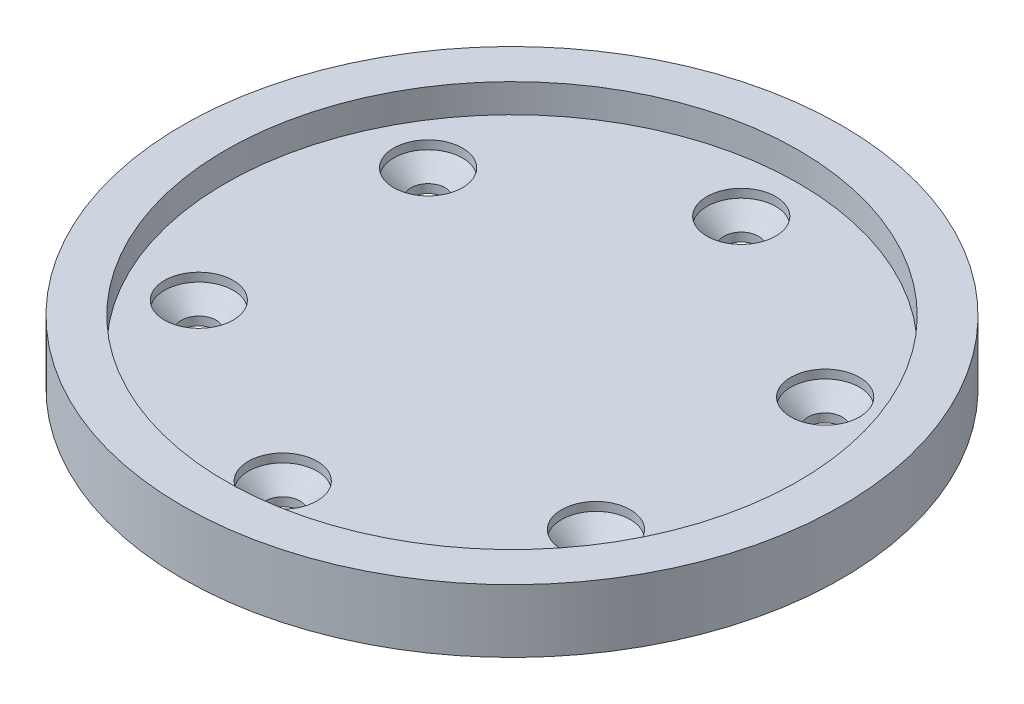
SolidWorks part; units mm, degrees
material "PBT General Purpose"
ref_plane "Front Plane" through (0, 0, 0) normal (0, 0, 1) x (1, 0, 0)
ref_plane "Top Plane" through (0, 0, 0) normal (0, 1, 0) x (1, 0, 0)
ref_plane "Right Plane" through (0, 0, 0) normal (1, 0, 0) x (0, 0, -1)
sketch "Sketch1" plane through (0, 0, 0) normal (0, 0, 1) x (1, 0, 0)
  line L0 (0, 0) -> (0, 21.4941) construction
  line L1 (50, 5.4786) -> (50, 10.4786)
  line L2 (50, 10.4786) -> (57.5, 10.4786)
  line L9 (50, 5.4786) -> (0, 5.4786)
  line L10 (0, -0.5214) -> (0, 5.4786)
  line L11 (0, -0.5214) -> (57.5, -0.5214)
  line L12 (57.5, -0.5214) -> (57.5, 10.4786)
  dimension "D1" = 0.5214
  dimension "D2" = 50
  dimension "D5" = 7.5
  dimension "D3" = 6
  dimension "D7" = 5
revolve "Revolve1" add sketch "Sketch1" angle 360 about L0
sketch "Sketch2" plane through (0, 5.4786, 0) normal (0, 1, 0) x (1, 0, 0)
  line L0 (0, 0) -> (0, 40) construction
  circle A0 centre (0, 40) radius 3
  circle A6 centre (34.641, 20) radius 3
  circle A7 centre (34.641, -20) radius 3
  circle A8 centre (0, -40) radius 3
  circle A9 centre (-34.641, -20) radius 3
  circle A10 centre (-34.641, 20) radius 3
  point P31 (0, 0)
  dimension "D1" = 6
  dimension "D2" = 40
  dimension "D3" = 6
extrude "Cut-Extrude1" cut sketch "Sketch2" against normal through all
sketch "Sketch3" plane through (0, 5.4786, 0) normal (0, 1, 0) x (1, 0, 0)
  circle A0 centre (0, 40) radius 6
  circle A1 centre (34.641, 20) radius 6
  circle A2 centre (34.641, -20) radius 6
  circle A3 centre (0, -40) radius 6
  circle A4 centre (-34.641, -20) radius 6
  circle A5 centre (-34.641, 20) radius 6
  point P3 (0, 0)
  point P18 (0, 0)
  dimension "D1" = 12
  dimension "D2" = 6
extrude "Cut-Extrude2" cut sketch "Sketch3" against normal blind 1.5
chamfer "Chamfer1" distance 3 angle 45 6 edges at (-34.641, 3.9786, -17) (-34.641, 3.9786, 23) (0, 3.9786, 43) (0, 3.9786, -37) (34.641, 3.9786, -17) (34.641, 3.9786, 23)
sketch "Avoid Area1" plane through (0, 10.4786, 0) normal (0, 1, 0) x (1, 0, 0)
  line L1 (-89.8447, 23.9111) -> (-38.4245, 23.9111)
  line L2 (-89.8447, 23.9111) -> (-89.8447, -17.7959)
  line L3 (-89.8447, -17.7959) -> (-38.4245, -17.7959)
  line L4 (-38.4245, 23.9111) -> (-38.4245, -17.7959)
  line L5 (40.0837, 23.0719) -> (89.3624, 23.0719)
  line L6 (40.0837, 23.0719) -> (40.0837, -19.2779)
  line L7 (40.0837, -19.2779) -> (89.3624, -19.2779)
  line L8 (89.3624, 23.0719) -> (89.3624, -19.2779)
sketch "Avoid Area2" plane through (0, 10.4786, 0) normal (0, 1, 0) x (1, 0, 0)
  line L5 (-29.0326, -25.7834) -> (28.925, -25.7834)
  line L6 (-29.0326, -25.7834) -> (-29.0326, -80.3919)
  line L11 (-29.0326, -80.3919) -> (28.925, -80.3919)
  line L12 (28.925, -25.7834) -> (28.925, -80.3919)
  line L13 (-25.225, 88.174) -> (28.7215, 88.174)
  line L14 (-25.225, 88.174) -> (-25.225, 29.095)
  line L15 (-25.225, 29.095) -> (28.7215, 29.095)
  line L16 (28.7215, 88.174) -> (28.7215, 29.095)
  point P0 (0, 0)
  point P6 (0, 0)
sketch3d "3DSketch3"
  point P0 (-59.5, 29.4786, 59.5)
